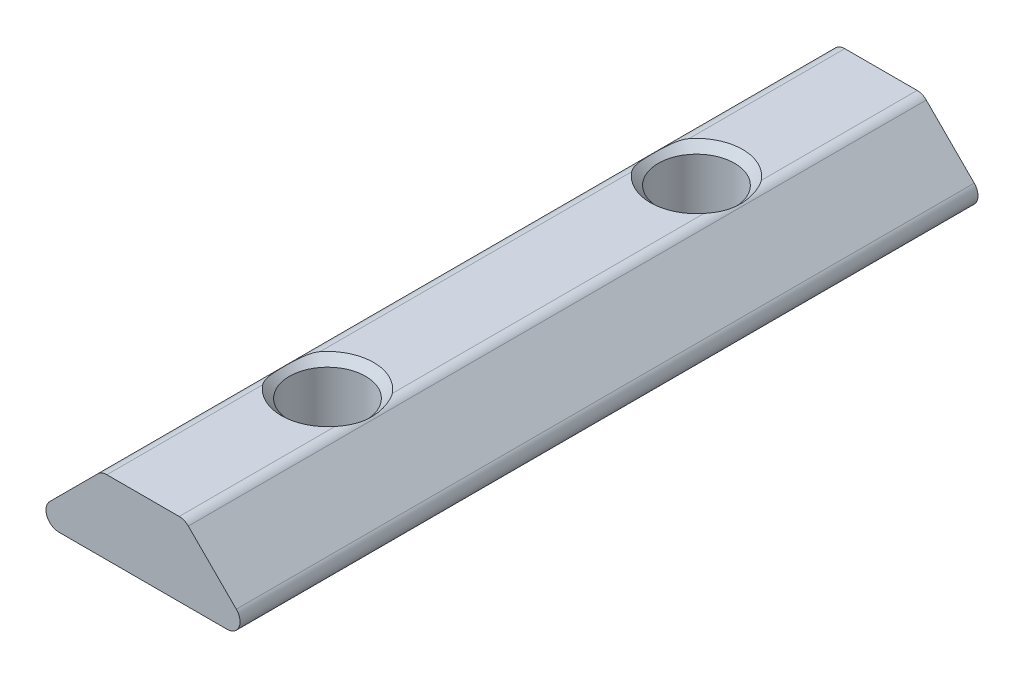
SolidWorks part; units mm, degrees
ref_plane "Front Plane" through (0, 0, 0) normal (0, 0, 1) x (1, 0, 0)
ref_plane "Top Plane" through (0, 0, 0) normal (0, 1, 0) x (1, 0, 0)
ref_plane "Right Plane" through (0, 0, 0) normal (1, 0, 0) x (0, 0, -1)
sketch "Sketch1" plane through (0, 0, 0) normal (0, 0, 1) x (1, 0, 0)
  line L0 (-4.5601, 0) -> (4.5601, 0)
  line L1 (5.055, 1.195) -> (2.455, 3.795)
  line L2 (1.9601, 4) -> (-1.9601, 4)
  line L3 (-2.455, 3.795) -> (-5.055, 1.195)
  arc A0 (-5.055, 1.195) -> (-4.5601, 0) centre (-4.5601, 0.7) ccw
  arc A1 (4.5601, 0) -> (5.055, 1.195) centre (4.5601, 0.7) ccw
  arc A2 (2.455, 3.795) -> (1.9601, 4) centre (1.9601, 3.3) ccw
  arc A3 (-1.9601, 4) -> (-2.455, 3.795) centre (-1.9601, 3.3) ccw
extrude "Boss-Extrude1" add sketch "Sketch1" against normal blind 20 and the other way blind 20
sketch "Sketch2" plane through (0, 0, 0) normal (1, 0, 0) x (0, 0, -1)
  line L0 (-10, 4) -> (-7.5, 4)
  line L1 (-7.5, 4) -> (-7.933, 3.567)
  line L2 (-7.933, 3.567) -> (-7.933, 0.433)
  line L3 (-7.933, 0.433) -> (-7.5, 0)
  line L4 (-7.5, 0) -> (-10, 0)
  line L5 (-10, 0) -> (-10, 4)
  line L6 (-10, 0) -> (-10, 4) construction
revolve "Cut-Revolve1" cut sketch "Sketch2" angle 360 about L6 reverse direction yes
cosmetic thread "Cosmetic Thread1" parameters "D1"=4, "D2"=5
sketch "Sketch3" plane through (0, 0, 0) normal (1, 0, 0) x (0, 0, -1)
  line L0 (10, 4) -> (12.5, 4)
  line L1 (12.5, 4) -> (12.067, 3.567)
  line L2 (12.067, 3.567) -> (12.067, 0.433)
  line L3 (12.067, 0.433) -> (12.5, 0)
  line L4 (12.5, 0) -> (10, 0)
  line L5 (10, 0) -> (10, 4)
  line L6 (10, 0) -> (10, 4) construction
revolve "Cut-Revolve2" cut sketch "Sketch3" angle 360 about L6 reverse direction yes
cosmetic thread "Cosmetic Thread2" parameters "D1"=4, "D2"=5
ref_plane "NUT XY" through (0, 0, 0) normal (0, 1, 0) x (1, 0, 0)
ref_plane "NUT XZ" through (0, 0, 10) normal (0, 0, 1) x (1, 0, 0)
ref_plane "NUT YZ" through (0, 0, 0) normal (1, 0, 0) x (0, 0, -1)
ref_axis "NUT X" through (-80.9, 0, 10) along (1, 0, 0)
ref_axis "NUT Y" through (0, 0, 50) along (0, 0, -1)
ref_axis "NUT Z" through (0, 50, 10) along (0, -1, 0)
sketch3d "NUT"
  point P0 (0, 0, 10)
other "Freeze***"
